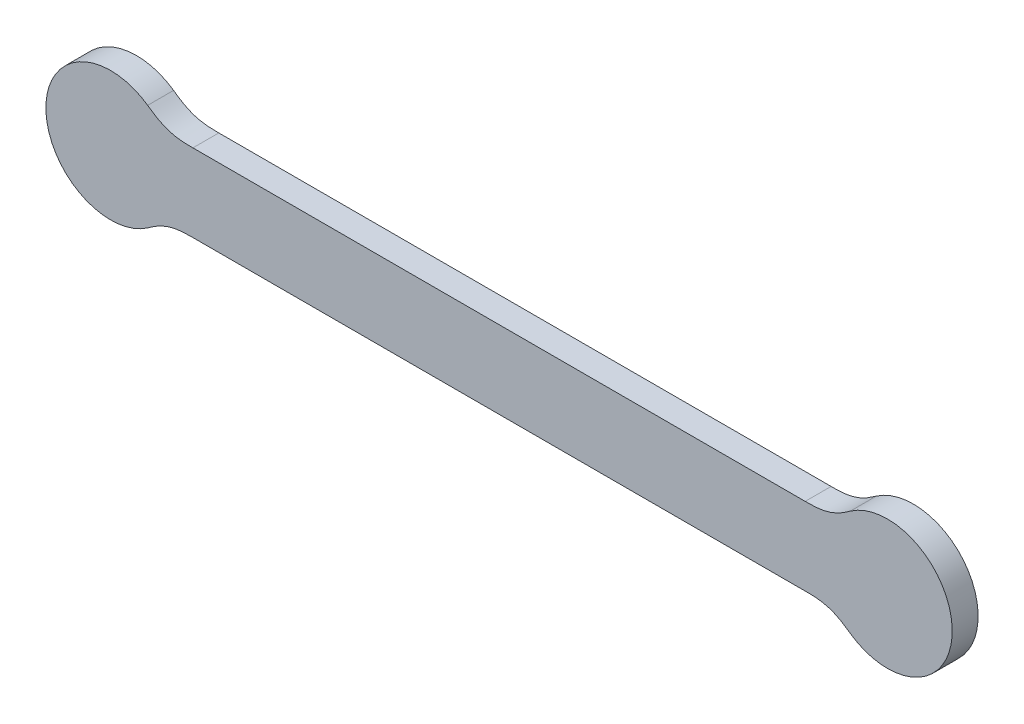
SolidWorks part; units mm, degrees
ref_plane "前基準面" through (0, 0, 0) normal (0, 0, 1) x (1, 0, 0)
ref_plane "上基準面" through (0, 0, 0) normal (0, 1, 0) x (1, 0, 0)
ref_plane "右基準面" through (0, 0, 0) normal (1, 0, 0) x (0, 0, -1)
sketch "草圖2" plane through (0, 0, 0) normal (0, 0, 1) x (1, 0, 0)
  line L2 (63.561, -30) -> (536.439, -30)
  line L3 (63.561, -30) -> (536.439, -30)
  line L6 (536.439, 30) -> (63.561, 30)
  line L7 (536.439, 30) -> (63.561, 30)
  arc A2 (28.6311, 40.991) -> (28.6311, -40.991) centre (0, 0) ccw
  arc A3 (28.6311, 40.991) -> (28.6311, -40.991) centre (0, 0) ccw
  arc A6 (571.3689, -40.991) -> (571.3689, 40.991) centre (600, 0) ccw
  arc A7 (571.3689, -40.991) -> (571.3689, 40.991) centre (600, 0) ccw
  spline S4 degree 2 poles (1623.8096, 1165.4057) (-17.0757, -73.4635) (29.1104, -40.6529) (29.2456, -40.5569) (29.5882, -40.3124) (29.8901, -40.0969) (30.066, -39.9718) (30.3292, -39.7847) (30.5448, -39.6327) (31.0522, -39.2751) (31.5075, -38.9631) (32.0025, -38.6237) (32.4793, -38.3081) (33.4752, -37.6488) (34.4553, -37.0503) (35.469, -36.4312) (36.4787, -35.8687) (37.5204, -35.2884) (38.5539, -34.7706) (39.6224, -34.2352) (40.6782, -33.7689) (41.7628, -33.2899) (42.8374, -32.8826) (43.9313, -32.468) (45.0336, -32.1212) (46.1354, -31.7745) (47.2676, -31.488) (48.3849, -31.2053) (49.5386, -30.9798) (50.669, -30.7588) (51.8448, -30.5909) (52.9822, -30.4286) (54.1793, -30.3137) (55.3082, -30.2055) (56.5205, -30.1369) (57.628, -30.0743) (58.8652, -30.0419) (59.4255, -30.0271) (60.0386, -30.0179) (60.5901, -30.0096) (61.2124, -30.0054) (61.7347, -30.0018) (62.3866, -30.0007) (91.1691, -29.9508) (2063.4801, -33.5377) knots -2.676133 -2.676133 -2.676133 0.015625 0.015625 0.03125 0.03125 0.046875 0.046875 0.0625 0.0625 0.09375 0.09375 0.125 0.125 0.1875 0.1875 0.25 0.25 0.3125 0.3125 0.375 0.375 0.4375 0.4375 0.5 0.5 0.5625 0.5625 0.625 0.625 0.6875 0.6875 0.75 0.75 0.8125 0.8125 0.875 0.875 0.90625 0.90625 0.9375 0.9375 0.96875 0.96875 3.218826 3.218826 3.218826 only from (28.6311, -40.991) to (63.561, -30)
  spline S5 degree 2 poles (28.6311, -40.991) (28.8423, -40.8434) (29.1104, -40.6529) (29.2456, -40.5569) (29.5882, -40.3124) (29.8901, -40.0969) (30.066, -39.9718) (30.3292, -39.7847) (30.5448, -39.6327) (31.0522, -39.2751) (31.5075, -38.9631) (32.0025, -38.6237) (32.4793, -38.3081) (33.4752, -37.6488) (34.4553, -37.0503) (35.469, -36.4312) (36.4787, -35.8687) (37.5204, -35.2884) (38.5539, -34.7706) (39.6224, -34.2352) (40.6782, -33.7689) (41.7628, -33.2899) (42.8374, -32.8826) (43.9313, -32.468) (45.0336, -32.1212) (46.1354, -31.7745) (47.2676, -31.488) (48.3849, -31.2053) (49.5386, -30.9798) (50.669, -30.7588) (51.8448, -30.5909) (52.9822, -30.4286) (54.1793, -30.3137) (55.3082, -30.2055) (56.5205, -30.1369) (57.628, -30.0743) (58.8652, -30.0419) (59.4255, -30.0271) (60.0386, -30.0179) (60.5901, -30.0096) (61.2124, -30.0054) (61.7347, -30.0018) (62.3866, -30.0007) (62.7864, -30) (63.561, -30) knots 0 0 0 0.015625 0.015625 0.03125 0.03125 0.046875 0.046875 0.0625 0.0625 0.09375 0.09375 0.125 0.125 0.1875 0.1875 0.25 0.25 0.3125 0.3125 0.375 0.375 0.4375 0.4375 0.5 0.5 0.5625 0.5625 0.625 0.625 0.6875 0.6875 0.75 0.75 0.8125 0.8125 0.875 0.875 0.90625 0.90625 0.9375 0.9375 0.96875 0.96875 1 1 1
  spline S6 degree 2 poles (-1463.5221, -33.5518) (508.7188, -29.9507) (537.6132, -30.0007) (538.264, -30.0018) (538.7872, -30.0054) (539.4083, -30.0096) (539.9608, -30.0179) (540.5725, -30.0271) (541.1337, -30.0418) (542.3692, -30.0742) (543.4772, -30.1368) (544.6875, -30.2052) (545.8165, -30.3133) (547.012, -30.4279) (548.1505, -30.5903) (549.3295, -30.7584) (550.4655, -30.9806) (551.6206, -31.2065) (552.7413, -31.4903) (553.8729, -31.7768) (554.9763, -32.1243) (556.0762, -32.4706) (557.1695, -32.8852) (558.2401, -33.2912) (559.3222, -33.7691) (560.3725, -34.2329) (561.4377, -34.7664) (562.471, -35.2838) (563.515, -35.8652) (564.5253, -36.4278) (565.5413, -37.0482) (566.5215, -37.6467) (567.5191, -38.3071) (567.9953, -38.6222) (568.4916, -38.9624) (568.9461, -39.2739) (569.4547, -39.6323) (569.6695, -39.7837) (569.9335, -39.9715) (570.1088, -40.0962) (570.4115, -40.3122) (570.7539, -40.5565) (570.8894, -40.6528) (617.2884, -73.6153) (-1023.2419, 1166.0688) knots -2.223549 -2.223549 -2.223549 0.03125 0.03125 0.0625 0.0625 0.09375 0.09375 0.125 0.125 0.1875 0.1875 0.25 0.25 0.3125 0.3125 0.375 0.375 0.4375 0.4375 0.5 0.5 0.5625 0.5625 0.625 0.625 0.6875 0.6875 0.75 0.75 0.8125 0.8125 0.875 0.875 0.90625 0.90625 0.9375 0.9375 0.953125 0.953125 0.96875 0.96875 0.984375 0.984375 3.690873 3.690873 3.690873 only from (536.439, -30) to (571.3689, -40.991)
  spline S7 degree 2 poles (536.439, -30) (537.2127, -30) (537.6132, -30.0007) (538.264, -30.0018) (538.7872, -30.0054) (539.4083, -30.0096) (539.9608, -30.0179) (540.5725, -30.0271) (541.1337, -30.0418) (542.3692, -30.0742) (543.4772, -30.1368) (544.6875, -30.2052) (545.8165, -30.3133) (547.012, -30.4279) (548.1505, -30.5903) (549.3295, -30.7584) (550.4655, -30.9806) (551.6206, -31.2065) (552.7413, -31.4903) (553.8729, -31.7768) (554.9763, -32.1243) (556.0762, -32.4706) (557.1695, -32.8852) (558.2401, -33.2912) (559.3222, -33.7691) (560.3725, -34.2329) (561.4377, -34.7664) (562.471, -35.2838) (563.515, -35.8652) (564.5253, -36.4278) (565.5413, -37.0482) (566.5215, -37.6467) (567.5191, -38.3071) (567.9953, -38.6222) (568.4916, -38.9624) (568.9461, -39.2739) (569.4547, -39.6323) (569.6695, -39.7837) (569.9335, -39.9715) (570.1088, -40.0962) (570.4115, -40.3122) (570.7539, -40.5565) (570.8894, -40.6528) (571.1573, -40.8431) (571.3689, -40.991) knots 0 0 0 0.03125 0.03125 0.0625 0.0625 0.09375 0.09375 0.125 0.125 0.1875 0.1875 0.25 0.25 0.3125 0.3125 0.375 0.375 0.4375 0.4375 0.5 0.5 0.5625 0.5625 0.625 0.625 0.6875 0.6875 0.75 0.75 0.8125 0.8125 0.875 0.875 0.90625 0.90625 0.9375 0.9375 0.953125 0.953125 0.96875 0.96875 0.984375 0.984375 1 1 1
  spline S8 degree 2 poles (-1023.8096, -1165.4058) (617.0757, 73.4635) (570.8896, 40.6529) (570.7544, 40.5569) (570.4118, 40.3124) (570.1099, 40.0969) (569.934, 39.9718) (569.6708, 39.7847) (569.4552, 39.6327) (568.9478, 39.2751) (568.4925, 38.9631) (567.9975, 38.6237) (567.5207, 38.3081) (566.5248, 37.6488) (565.5447, 37.0503) (564.531, 36.4312) (563.5213, 35.8687) (562.4796, 35.2884) (561.4461, 34.7706) (560.3776, 34.2352) (559.3218, 33.7689) (558.2372, 33.2899) (557.1626, 32.8826) (556.0687, 32.468) (554.9664, 32.1212) (553.8646, 31.7745) (552.7324, 31.488) (551.6151, 31.2053) (550.4614, 30.9798) (549.331, 30.7588) (548.1552, 30.5909) (547.0178, 30.4286) (545.8207, 30.3137) (544.6918, 30.2055) (543.4795, 30.1369) (542.372, 30.0743) (541.1348, 30.0419) (540.5745, 30.0271) (539.9614, 30.0179) (539.4099, 30.0096) (538.7876, 30.0054) (538.2653, 30.0018) (537.6134, 30.0007) (508.8309, 29.9508) (-1463.4801, 33.5377) knots -2.676133 -2.676133 -2.676133 0.015625 0.015625 0.03125 0.03125 0.046875 0.046875 0.0625 0.0625 0.09375 0.09375 0.125 0.125 0.1875 0.1875 0.25 0.25 0.3125 0.3125 0.375 0.375 0.4375 0.4375 0.5 0.5 0.5625 0.5625 0.625 0.625 0.6875 0.6875 0.75 0.75 0.8125 0.8125 0.875 0.875 0.90625 0.90625 0.9375 0.9375 0.96875 0.96875 3.218826 3.218826 3.218826 only from (571.3689, 40.991) to (536.439, 30)
  spline S9 degree 2 poles (571.3689, 40.991) (571.1577, 40.8434) (570.8896, 40.6529) (570.7544, 40.5569) (570.4118, 40.3124) (570.1099, 40.0969) (569.934, 39.9718) (569.6708, 39.7847) (569.4552, 39.6327) (568.9478, 39.2751) (568.4925, 38.9631) (567.9975, 38.6237) (567.5207, 38.3081) (566.5248, 37.6488) (565.5447, 37.0503) (564.531, 36.4312) (563.5213, 35.8687) (562.4796, 35.2884) (561.4461, 34.7706) (560.3776, 34.2352) (559.3218, 33.7689) (558.2372, 33.2899) (557.1626, 32.8826) (556.0687, 32.468) (554.9664, 32.1212) (553.8646, 31.7745) (552.7324, 31.488) (551.6151, 31.2053) (550.4614, 30.9798) (549.331, 30.7588) (548.1552, 30.5909) (547.0178, 30.4286) (545.8207, 30.3137) (544.6918, 30.2055) (543.4795, 30.1369) (542.372, 30.0743) (541.1348, 30.0419) (540.5745, 30.0271) (539.9614, 30.0179) (539.4099, 30.0096) (538.7876, 30.0054) (538.2653, 30.0018) (537.6134, 30.0007) (537.2136, 30) (536.439, 30) knots 0 0 0 0.015625 0.015625 0.03125 0.03125 0.046875 0.046875 0.0625 0.0625 0.09375 0.09375 0.125 0.125 0.1875 0.1875 0.25 0.25 0.3125 0.3125 0.375 0.375 0.4375 0.4375 0.5 0.5 0.5625 0.5625 0.625 0.625 0.6875 0.6875 0.75 0.75 0.8125 0.8125 0.875 0.875 0.90625 0.90625 0.9375 0.9375 0.96875 0.96875 1 1 1
  spline S10 degree 2 poles (2063.5221, 33.5518) (91.2812, 29.9507) (62.3868, 30.0007) (61.736, 30.0018) (61.2128, 30.0054) (60.5917, 30.0096) (60.0392, 30.0179) (59.4275, 30.0271) (58.8663, 30.0418) (57.6308, 30.0742) (56.5228, 30.1368) (55.3125, 30.2052) (54.1835, 30.3133) (52.988, 30.4279) (51.8495, 30.5903) (50.6705, 30.7584) (49.5345, 30.9806) (48.3794, 31.2065) (47.2587, 31.4903) (46.1271, 31.7768) (45.0237, 32.1243) (43.9238, 32.4706) (42.8305, 32.8852) (41.7599, 33.2912) (40.6778, 33.7691) (39.6275, 34.2329) (38.5623, 34.7664) (37.529, 35.2838) (36.485, 35.8652) (35.4747, 36.4278) (34.4587, 37.0482) (33.4785, 37.6467) (32.4809, 38.3071) (32.0047, 38.6222) (31.5084, 38.9624) (31.0539, 39.2739) (30.5453, 39.6323) (30.3305, 39.7837) (30.0665, 39.9715) (29.8912, 40.0962) (29.5885, 40.3122) (29.2461, 40.5565) (29.1106, 40.6528) (-17.2884, 73.6153) (1623.242, -1166.0689) knots -2.223549 -2.223549 -2.223549 0.03125 0.03125 0.0625 0.0625 0.09375 0.09375 0.125 0.125 0.1875 0.1875 0.25 0.25 0.3125 0.3125 0.375 0.375 0.4375 0.4375 0.5 0.5 0.5625 0.5625 0.625 0.625 0.6875 0.6875 0.75 0.75 0.8125 0.8125 0.875 0.875 0.90625 0.90625 0.9375 0.9375 0.953125 0.953125 0.96875 0.96875 0.984375 0.984375 3.690873 3.690873 3.690873 only from (63.561, 30) to (28.6311, 40.991)
  spline S11 degree 2 poles (63.561, 30) (62.7873, 30) (62.3868, 30.0007) (61.736, 30.0018) (61.2128, 30.0054) (60.5917, 30.0096) (60.0392, 30.0179) (59.4275, 30.0271) (58.8663, 30.0418) (57.6308, 30.0742) (56.5228, 30.1368) (55.3125, 30.2052) (54.1835, 30.3133) (52.988, 30.4279) (51.8495, 30.5903) (50.6705, 30.7584) (49.5345, 30.9806) (48.3794, 31.2065) (47.2587, 31.4903) (46.1271, 31.7768) (45.0237, 32.1243) (43.9238, 32.4706) (42.8305, 32.8852) (41.7599, 33.2912) (40.6778, 33.7691) (39.6275, 34.2329) (38.5623, 34.7664) (37.529, 35.2838) (36.485, 35.8652) (35.4747, 36.4278) (34.4587, 37.0482) (33.4785, 37.6467) (32.4809, 38.3071) (32.0047, 38.6222) (31.5084, 38.9624) (31.0539, 39.2739) (30.5453, 39.6323) (30.3305, 39.7837) (30.0665, 39.9715) (29.8912, 40.0962) (29.5885, 40.3122) (29.2461, 40.5565) (29.1106, 40.6528) (28.8427, 40.8431) (28.6311, 40.991) knots 0 0 0 0.03125 0.03125 0.0625 0.0625 0.09375 0.09375 0.125 0.125 0.1875 0.1875 0.25 0.25 0.3125 0.3125 0.375 0.375 0.4375 0.4375 0.5 0.5 0.5625 0.5625 0.625 0.625 0.6875 0.6875 0.75 0.75 0.8125 0.8125 0.875 0.875 0.90625 0.90625 0.9375 0.9375 0.953125 0.953125 0.96875 0.96875 0.984375 0.984375 1 1 1
  dimension "D1" = 0
extrude "填料-伸長1" add sketch "草圖2" along normal blind 20
shell "薄殼1" [suppressed] thickness 10
fillet "圓角1" radius 3 rebuild error yes
equation "\"D1@薄殼1\"=\"shell_thick@零件5^組合件1-1.Part\""
